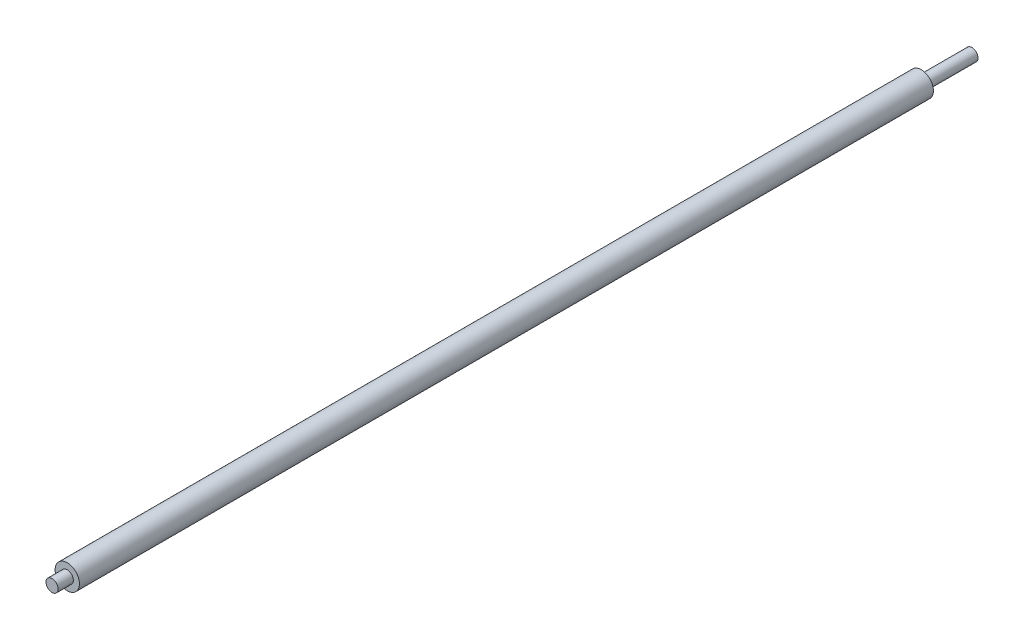
SolidWorks part; units mm, degrees
ref_plane "Front Plane" through (0, 0, 0) normal (0, 0, 1) x (1, 0, 0)
ref_plane "Top Plane" through (0, 0, 0) normal (0, 1, 0) x (1, 0, 0)
ref_plane "Right Plane" through (0, 0, 0) normal (1, 0, 0) x (0, 0, -1)
sketch "Sketch1" plane through (0, 0, 0) normal (0, 0, 1) x (1, 0, 0)
  circle A0 centre (0, 0) radius 6
  dimension "D1" = 12
extrude "Boss-Extrude1" add sketch "Sketch1" along normal mid plane 421.5
sketch "Sketch2" plane through (0, 0, 210.75) normal (0, 0, 1) x (1, 0, 0)
  circle A1 centre (0, 0) radius 3
  dimension "D2" = 6
sketch "Sketch3" plane through (0, 0, -210.75) normal (0, 0, -1) x (-1, 0, 0)
  circle A1 centre (0, 0) radius 3
  dimension "D1" = 6
extrude "Boss-Extrude4" add sketch "Sketch2" along normal blind 7.5
extrude "Boss-Extrude5" add sketch "Sketch3" along normal blind 25
